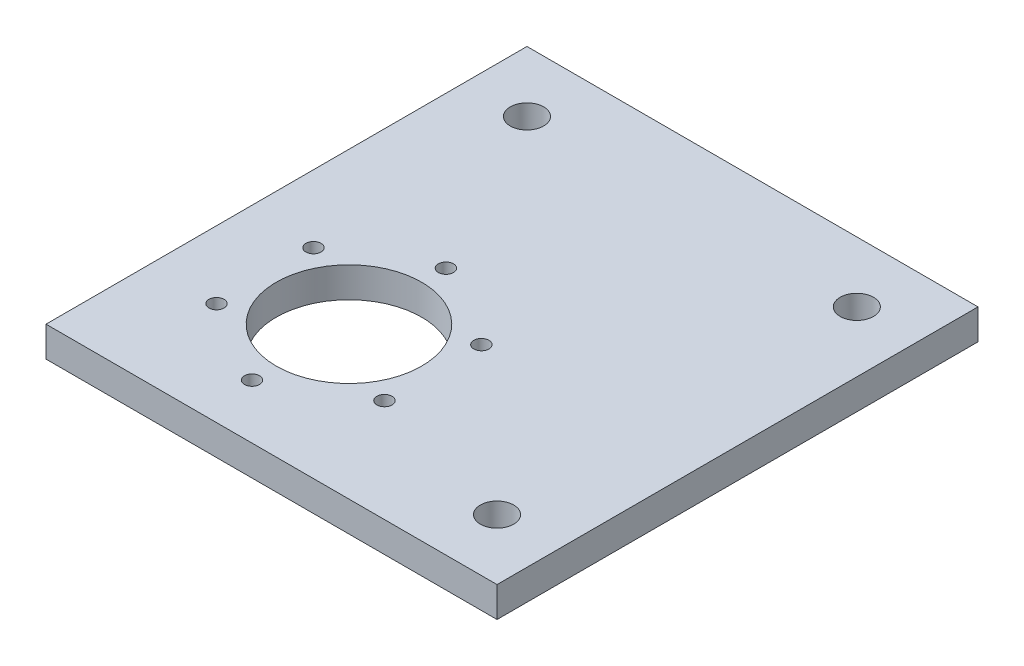
SolidWorks part; units mm, degrees
ref_plane "Front Plane" through (0, 0, 0) normal (0, 0, 1) x (1, 0, 0)
ref_plane "Top Plane" through (0, 0, 0) normal (0, 1, 0) x (1, 0, 0)
ref_plane "Right Plane" through (0, 0, 0) normal (1, 0, 0) x (0, 0, -1)
sketch "Sketch2" plane through (0, 0, 0) normal (0, 1, 0) x (1, 0, 0)
  line L1 (-18.6933, 53.5256) -> (55.7467, 53.5256)
  line L2 (-18.6933, 53.5256) -> (-18.6933, -25.8544)
  line L3 (-18.6933, -25.8544) -> (55.7467, -25.8544)
  line L4 (55.7467, 53.5256) -> (55.7467, -25.8544)
  circle A0 centre (6.3067, -0.8544) radius 12
  dimension "D1" = 24
  dimension "D2" = 74.44
  dimension "D3" = 79.38
extrude "Boss-Extrude1" add sketch "Sketch2" along normal blind 5
sketch "Sketch4" plane through (0, 5, 0) normal (0, 1, 0) x (1, 0, 0)
  circle A0 centre (6.3067, 15.1456) radius 1.25 construction
  circle A1 centre (6.3067, 15.1456) radius 1.25
  circle A2 centre (6.3067, -16.8544) radius 1.25 construction
  circle A3 centre (6.3067, -16.8544) radius 1.25
  circle A4 centre (-7.5497, -8.8544) radius 1.25 construction
  circle A5 centre (-7.5497, -8.8544) radius 1.25
  circle A6 centre (-7.5497, -8.8544) radius 1.25 construction
  circle A7 centre (-7.5497, -8.8544) radius 1.25
  circle A8 centre (-7.5497, 7.1456) radius 1.25 construction
  circle A9 centre (-7.5497, 7.1456) radius 1.25
  circle A10 centre (20.1631, 7.1456) radius 1.25 construction
  circle A11 centre (20.1631, 7.1456) radius 1.25
  circle A12 centre (20.1631, -8.8544) radius 1.25 construction
  circle A13 centre (20.1631, -8.8544) radius 1.25
sketch "Sketch5" plane through (0, 5, 0) normal (0, 1, 0) x (1, 0, 0)
  circle A0 centre (6.3067, 15.1456) radius 1.25
  circle A1 centre (20.1631, 7.1456) radius 1.25
  circle A2 centre (20.1631, -8.8544) radius 1.25
  circle A4 centre (6.3067, -16.8544) radius 1.25
  circle A5 centre (-7.5497, -8.8544) radius 1.25
  circle A6 centre (-7.5497, 7.1456) radius 1.25
  dimension "D1" = 2.5
  dimension "D2" = 2.5
  dimension "D3" = 2.5
  dimension "D4" = 2.5
  dimension "D5" = 2.5
  dimension "D6" = 2.5
extrude "Cut-Extrude1" cut sketch "Sketch5" against normal blind 6
sketch "Sketch6" plane through (0, 0, 0) normal (0, -1, 0) x (1, 0, 0)
  line L0 (55.7467, 25.8544) -> (55.7467, -53.5256) construction
  line L1 (55.7467, -53.5256) -> (-18.6933, -53.5256) construction
  line L2 (-18.6933, 25.8544) -> (55.7467, 25.8544) construction
  line L3 (-18.6933, -53.5256) -> (-18.6933, 25.8544) construction
  circle A0 centre (45.7467, 15.8544) radius 2.75
  circle A2 centre (45.7467, -43.5256) radius 2.75
  circle A3 centre (-8.6933, -43.5256) radius 2.75
  dimension "D5" = 5.5
  dimension "D6" = 5.5
  dimension "D7" = 5.5
  dimension "D1" = 10
  dimension "D2" = 10
  dimension "D3" = 10
  dimension "D4" = 10
extrude "Cut-Extrude2" cut sketch "Sketch6" against normal blind 10
